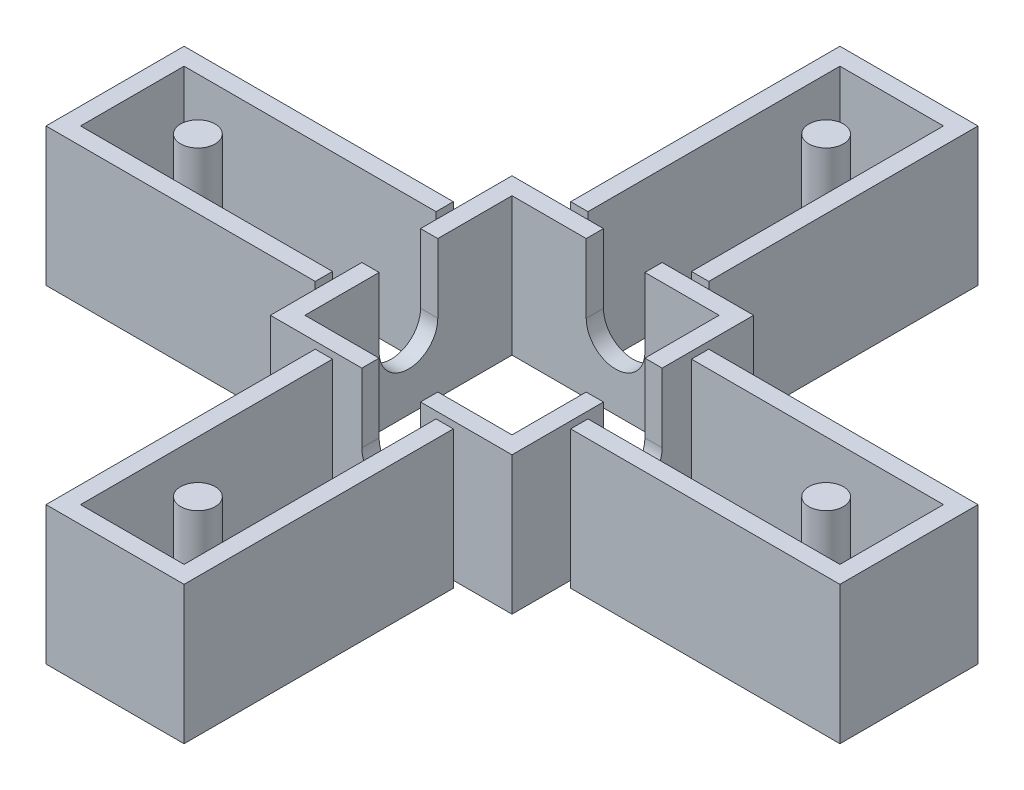
SolidWorks part; units mm, degrees
ref_plane "Front Plane" through (0, 0, 0) normal (0, 0, 1) x (1, 0, 0)
ref_plane "Top Plane" through (0, 0, 0) normal (0, 1, 0) x (1, 0, 0)
ref_plane "Right Plane" through (0, 0, 0) normal (1, 0, 0) x (0, 0, -1)
sketch "Sketch1" plane through (0, 0, 0) normal (0, 1, 0) x (1, 0, 0)
  line L0 (17.5, 17.5) -> (-17.5, 17.5)
  line L1 (15, -15) -> (-15, -15)
  line L2 (15, -15) -> (15, 15)
  line L3 (15, 15) -> (-15, 15)
  line L4 (-15, -15) -> (-15, 15)
  line L5 (15, -15) -> (-15, 15) construction
  line L6 (15, 15) -> (-15, -15) construction
  line L7 (-17.5, -17.5) -> (-17.5, 17.5)
  line L8 (17.5, -17.5) -> (-17.5, -17.5)
  line L9 (17.5, -17.5) -> (17.5, 17.5)
  point P0 (0, 0)
  dimension "D1" = 30
  dimension "D2" = 2.5
extrude "Boss-Extrude1" add sketch "Sketch1" along normal blind 20
sketch "Sketch2" plane through (-17.5, 0, 0) normal (-1, 0, 0) x (0, 0, 1)
  line L0 (-17.5, 20) -> (17.5, 0) construction
  line L1 (-4.25, 10) -> (-4.25, 20)
  line L2 (-17.5, 20) -> (17.5, 20) construction
  line L3 (4.25, 10) -> (4.25, 20)
  line L4 (4.25, 20) -> (-4.25, 20)
  arc A0 (-4.25, 10) -> (4.25, 10) centre (0, 10) ccw
  dimension "D1" = 4.25
extrude "Cut-Extrude1" cut sketch "Sketch2" against normal up to next
ref_axis "Axis1" through (0, 0, 0) along (0, 1, 0)
pattern_circular "CirPattern1" count 4 over 360 about axis through (0, 0, 0) along (0, 1, 0) of "Cut-Extrude1"
sketch "Sketch5" plane through (0, 0, 0) normal (0, 1, 0) x (1, 0, 0)
  line L0 (7.5, 17.5) -> (7.5, 55)
  line L1 (17.5, 17.5) -> (-17.5, 17.5) construction
  line L2 (7.5, 55) -> (-7.5, 55)
  line L3 (-7.5, 55) -> (-7.5, 17.5)
  line L4 (10, 17.5) -> (10, 57.5)
  line L5 (10, 57.5) -> (-10, 57.5)
  line L6 (-10, 57.5) -> (-10, 17.5)
  line L7 (10, 17.5) -> (7.5, 17.5)
  line L8 (-7.5, 17.5) -> (-10, 17.5)
  line L9 (0, 17.5) -> (7.5, 17.5) construction
  line L10 (0, 17.5) -> (-7.5, 17.5) construction
  dimension "D2" = 20
  dimension "D3" = 40
  dimension "D1" = 2.5
extrude "Boss-Extrude2" add sketch "Sketch5" along normal up to surface (20 mm away) up to face at (12.25, 20, -12.25)
sketch "Sketch6" plane through (0, 0, -55) normal (0, 0, 1) x (1, 0, 0)
  line L0 (-7.5, 0) -> (7.5, 0) construction
  line L1 (2.5, 3) -> (-2.5, 3)
  line L2 (2.5, 3) -> (2.5, 0)
  line L3 (2.5, 0) -> (-2.5, 0)
  line L4 (-2.5, 3) -> (-2.5, 0)
  line L5 (2.5, 3) -> (-2.5, 0) construction
  line L6 (2.5, 0) -> (-2.5, 3) construction
  line L7 (0, 1.5) -> (0, 0) construction
  point P0 (0, 1.5)
  dimension "D1" = 3
  dimension "D2" = 5
extrude "Boss-Extrude3" add sketch "Sketch6" along normal blind 12
sketch "Sketch7" plane through (0, 3, 0) normal (0, 1, 0) x (1, 0, 0)
  line L0 (2.5, 43) -> (2.5, 55) construction
  line L1 (-2.5, 43) -> (-2.5, 55) construction
  line L2 (2.5, 43) -> (-2.5, 43) construction
  circle A0 centre (0, 45.5) radius 2.5
extrude "Boss-Extrude4" add sketch "Sketch7" along normal up to surface (17 mm away) up to face at (0, 20, -22.1)
pattern_circular "CirPattern6" count 4 over 360 about axis through (0, 0, 0) along (0, 1, 0) of "Boss-Extrude4", "Boss-Extrude3", "Boss-Extrude2"
sketch "Sketch8" plane through (0, 20, 0) normal (0, 1, 0) x (1, 0, 0)
  line L0 (10, 17.5) -> (7.5, 17.5)
  line L1 (-7.5, 17.5) -> (-10, 17.5)
  line L2 (-10, 17.5) -> (-10, 18.5)
  line L3 (-10, 57.5) -> (-10, 17.5) construction
  line L4 (-10, 18.5) -> (-7.5, 18.5)
  line L5 (-7.5, 17.5) -> (-7.5, 55) construction
  line L6 (-7.5, 18.5) -> (-7.5, 17.5)
  line L7 (10, 17.5) -> (10, 18.5)
  line L8 (10, 17.5) -> (10, 57.5) construction
  line L9 (10, 18.5) -> (7.5, 18.5)
  line L10 (7.5, 55) -> (7.5, 17.5) construction
  line L11 (7.5, 18.5) -> (7.5, 17.5)
  line L12 (17.5, -10) -> (17.5, -7.5)
  line L13 (17.5, 7.5) -> (17.5, 10)
  line L14 (17.5, 10) -> (18.5, 10)
  line L15 (18.5, 10) -> (18.5, 7.5)
  line L16 (18.5, 7.5) -> (17.5, 7.5)
  line L17 (17.5, -10) -> (18.5, -10)
  line L18 (18.5, -10) -> (18.5, -7.5)
  line L19 (18.5, -7.5) -> (17.5, -7.5)
  line L20 (-10, -17.5) -> (-7.5, -17.5)
  line L21 (7.5, -17.5) -> (10, -17.5)
  line L22 (10, -17.5) -> (10, -18.5)
  line L23 (10, -18.5) -> (7.5, -18.5)
  line L24 (7.5, -18.5) -> (7.5, -17.5)
  line L25 (-10, -17.5) -> (-10, -18.5)
  line L26 (-10, -18.5) -> (-7.5, -18.5)
  line L27 (-7.5, -18.5) -> (-7.5, -17.5)
  line L28 (-17.5, 10) -> (-17.5, 7.5)
  line L29 (-17.5, -7.5) -> (-17.5, -10)
  line L30 (-17.5, -10) -> (-18.5, -10)
  line L31 (-18.5, -10) -> (-18.5, -7.5)
  line L32 (-18.5, -7.5) -> (-17.5, -7.5)
  line L33 (-17.5, 10) -> (-18.5, 10)
  line L34 (-18.5, 10) -> (-18.5, 7.5)
  line L35 (-18.5, 7.5) -> (-17.5, 7.5)
  point P47 (0, 0)
  dimension "D1" = 1
  dimension "D2" = 4
extrude "Cut-Extrude4" cut sketch "Sketch8" against normal through all
